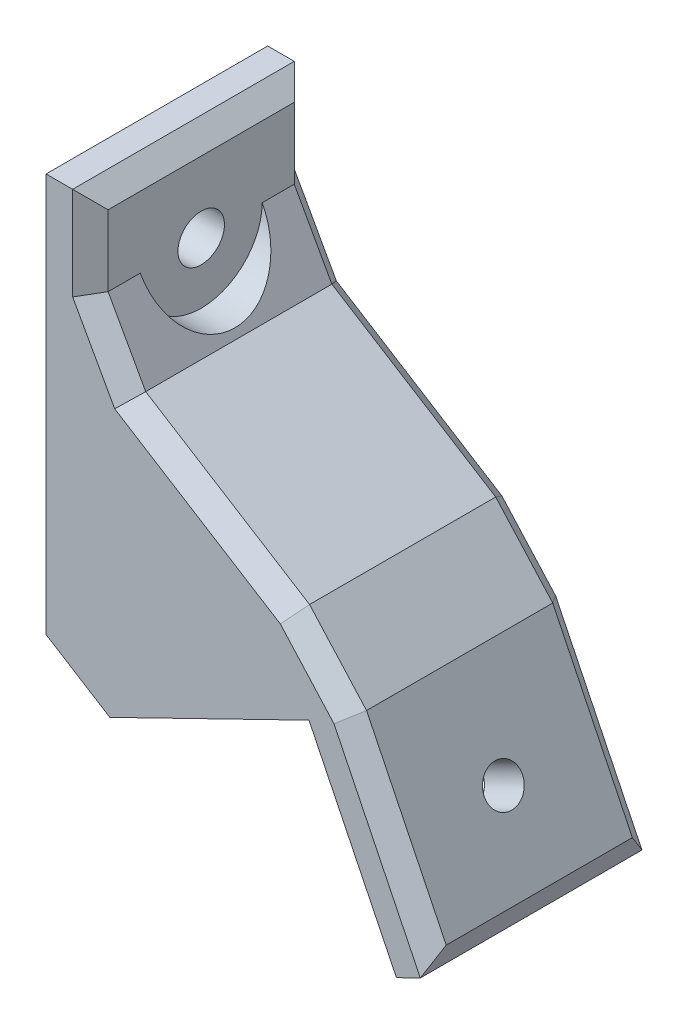
SolidWorks part; units mm, degrees
ref_plane "Plan de face" through (0, 0, 0) normal (0, 0, 1) x (1, 0, 0)
ref_plane "Plan de dessus" through (0, 0, 0) normal (0, 1, 0) x (1, 0, 0)
ref_plane "Plan de droite" through (0, 0, 0) normal (1, 0, 0) x (0, 0, -1)
sketch "Esquisse1" plane through (0, 0, 0) normal (0, 0, 1) x (1, 0, 0)
  line L0 (0, 0) -> (0, 20)
  line L1 (0, 20) -> (17.9759, 8.7674)
  line L2 (17.9759, 8.7674) -> (0, 0)
  dimension "D1" = 20
  dimension "D2" = 20
  dimension "D3" = 64
extrude "Boss.-Extru.1" add sketch "Esquisse1" along normal blind 20
sketch "Esquisse2" plane through (0, 0, 0) normal (-1, 0, 0) x (0, 0, 1)
  line L1 (0, 20) -> (20, 20)
  line L2 (0, 20) -> (0, 0)
  line L3 (0, 0) -> (20, 0)
  line L4 (20, 20) -> (20, 0)
extrude "Boss.-Extru.2" add sketch "Esquisse2" along normal blind 4
sketch "Esquisse3" plane through (0, 0, 0) normal (0.4384, -0.8988, 0) x (0.8988, 0.4384, 0)
  line L1 (0, 20) -> (20, 20)
  line L2 (0, 20) -> (0, 0)
  line L3 (0, 0) -> (20, 0)
  line L4 (20, 20) -> (20, 0)
extrude "Boss.-Extru.3" add sketch "Esquisse3" along normal blind 4
sketch "Esquisse4" plane through (0, 0, 20) normal (0, 0, 1) x (1, 0, 0)
  line L0 (-4, 20) -> (-4, 36)
  line L1 (-4, 36) -> (0, 36)
  line L2 (0, 20) -> (0, 36)
  line L3 (21.5711, 10.5209) -> (0, 24)
  line L4 (27.62, -11.006) -> (31.2152, -9.2526)
  line L5 (31.2152, -9.2526) -> (21.5711, 10.5209)
  line L6 (27.62, -11.006) -> (19.7294, 5.1722)
  line L7 (19.7294, 5.1722) -> (17.9759, 8.7674)
  line L8 (17.9759, 8.7674) -> (0, 20) construction
  line L9 (0, 20) -> (-4, 20)
  line L10 (21.5711, 10.5209) -> (17.9759, 8.7674)
  line L11 (-4, 0) -> (1.7535, -3.5952)
  line L12 (1.7535, -3.5952) -> (0, 0)
  line L13 (0, 0) -> (-4, 0)
  line M4 (19.7294, 5.1722) -> (17.9759, 8.7674)
  line M5 (17.9759, 8.7674) -> (0, 20)
  line M6 (0, 20) -> (-4, 20)
  dimension "D1" = 16
  dimension "D2" = 18
  dimension "D3" = 4
  dimension "D4" = 4
extrude "Boss.-Extru.4" add sketch "Esquisse4" against normal blind 20 contours L2 L1 L0 M6 | L10 L3 L2 M5 | L5 L10 L6 L4 M4 | L13 L11 L12 region at (-2, 28, 20) region at (9.914, 15.8657, 20) region at (24.5956, -0.2426, 20)
chamfer "Chanfrein1" distance 4 distance2 4 2 edges at (0, 24, 10) (21.5711, 10.5209, 10)
sketch "Esquisse5" plane through (-4, 0, 0) normal (-1, 0, 0) x (0, 0, 1)
  line L0 (0, 36) -> (20, 36) construction
  line L1 (0, 36) -> (0, 0) construction
  circle A0 centre (10, 28) radius 2.1
  dimension "D1" = 4.2
  dimension "D2" = 8
  dimension "D3" = 10
extrude "Enlèv. mat.-Extru.1" cut sketch "Esquisse5" against normal through all
sketch "Esquisse6" plane through (0, 0, 0) normal (1, 0, 0) x (0, 0, -1)
  circle A0 centre (-10, 28) radius 5.5
  dimension "D1" = 11
extrude "Enlèv. mat.-Extru.2" cut sketch "Esquisse6" along normal through all
hole_wizard "Dégagement #41" positions "Esquisse9" profile "Esquisse8" hole size "#4" standard "Ansi Inch"
sketch "Esquisse9" plane through (21.5711, 10.5209, 0) normal (0.8988, 0.4384, 0) x (0, 0, -1)
  line L0 (0, -22) -> (-20, -22) construction
  line L1 (0, -22) -> (0, -4) construction
  point P0 (-10, -13)
  dimension "D1" = 9
  dimension "D2" = 10
sketch "Esquisse8" plane through (27.2699, -1.1634, 10) normal (0, 0, 1) x (-0.4384, 0.8988, 0)
  line L0 (0, 0) -> (0, 11.0378)
  line L1 (0, 11.0378) -> (1.7272, 10)
  line L2 (1.7272, 10) -> (1.7272, 0)
  line L5 (1.7272, 0) -> (0, 0)
  line L10 (0, 11.0378) -> (-1.7272, 10) construction
  line L11 (0, -6.35) -> (0, 107.95) construction
  dimension "Diamètre du perçage" = 3.4544
  dimension "Profondeur du perçage" = 10
  dimension "Angle de pointe" = 118
chamfer "Chanfrein2" distance 1.6 angle 45 12 edges at (0, 32, 0) (0, 36, 10) (0, 32, 20) (1.6961, 24.9402, 0) (10.7855, 17.2605, 0) (20.7517, 9.7832, 0) (27.2699, -1.1634, 0) (31.2152, -9.2526, 10) (27.2699, -1.1634, 20) (20.7517, 9.7832, 20) (10.7855, 17.2605, 20) (1.6961, 24.9402, 20)
